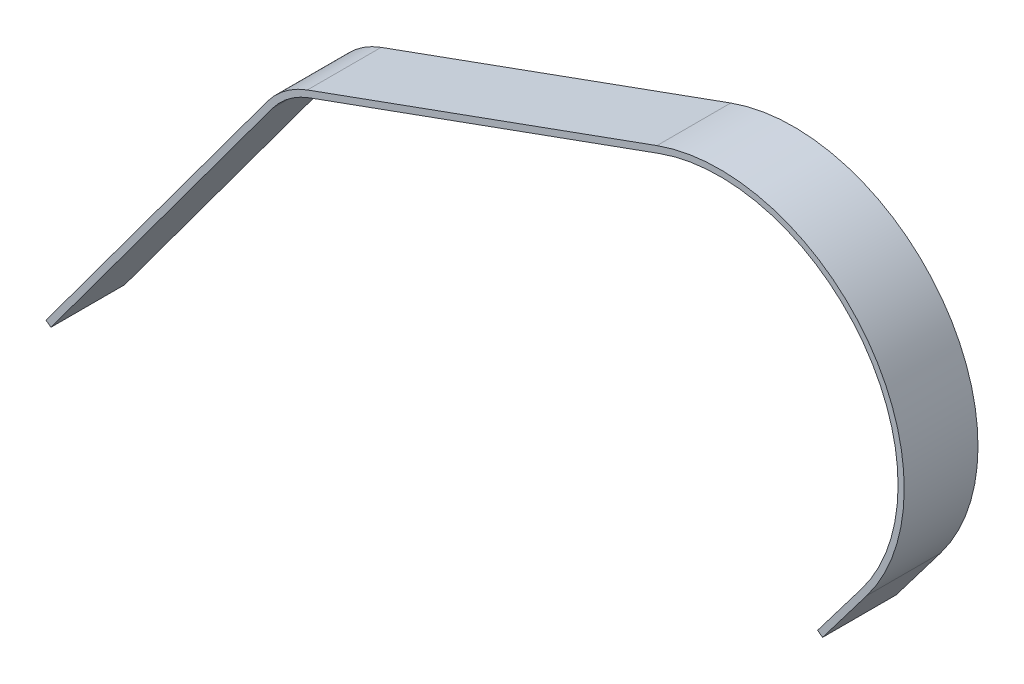
SolidWorks part; units mm, degrees
material "AISI 1020"
ref_plane "Front Plane" through (0, 0, 0) normal (0, 0, 1) x (1, 0, 0)
ref_plane "Top Plane" through (0, 0, 0) normal (0, 1, 0) x (1, 0, 0)
ref_plane "Right Plane" through (0, 0, 0) normal (1, 0, 0) x (0, 0, -1)
sketch "Sketch1" plane through (0, 0, 0) normal (0, 0, 1) x (1, 0, 0)
  line L0 (-36.5682, 0.9207) -> (143.9526, 66.3011)
  line L1 (-21.4316, -40.8727) -> (13.1807, -28.3369) construction
  line L6 (-36.5682, 0.9207) -> (-21.4316, -40.8727) construction
  line L14 (229.4691, -110.8747) -> (252.2647, -80.8348)
  line L15 (239.0655, -98.2286) -> (240.3301, -99.1882) construction
  line L19 (-57.2078, -14.4934) -> (-171.5307, -169.5402)
  line L23 (-163.3872, -155.8209) -> (-162.1095, -156.763) construction
  line L28 (143.9526, 66.3011) -> (194.1881, -72.4034) construction
  arc A0 (-57.2078, -14.4934) -> (-36.5682, 0.9207) centre (-21.4316, -40.8727) cw
  arc A10 (-190.1171, -186.0404) -> (-190.1067, -160.6404) centre (-190.1119, -173.3404) ccw construction
  arc A11 (143.9526, 66.3011) -> (252.2647, -80.8348) centre (176.3881, -23.2561) cw
  circle A12 centre (-21.4316, -40.8727) radius 6 construction
  circle A13 centre (231.071, -129.7727) radius 12.7 construction
  point P3 (261.2266, -66.5572)
  point P5 (-179.2656, -179.9471)
  point P7 (220.4922, -122.7458)
  point P8 (0, 0)
  point P9 (261.6582, -65.7011)
  point P10 (232.3285, -107.1065)
  point P12 (270.384, -28.3369)
  point P13 (270.6575, -59.2065)
  point P14 (0, 0)
  point P16 (-170.9405, -168.7397)
  point P17 (271.6381, -61.2704)
  point P19 (-20.3493, 9.3764)
  point P21 (258.3335, -75.5127)
  dimension "D5" = 44.45
  dimension "D3" = 15.875
  dimension "D2" = 95.25
  dimension "D1" = 15.875
extrude "Extrude-Thin1" add sketch "Sketch1" along normal blind 38.1 thin thin type one direction reverse wall 3.175
